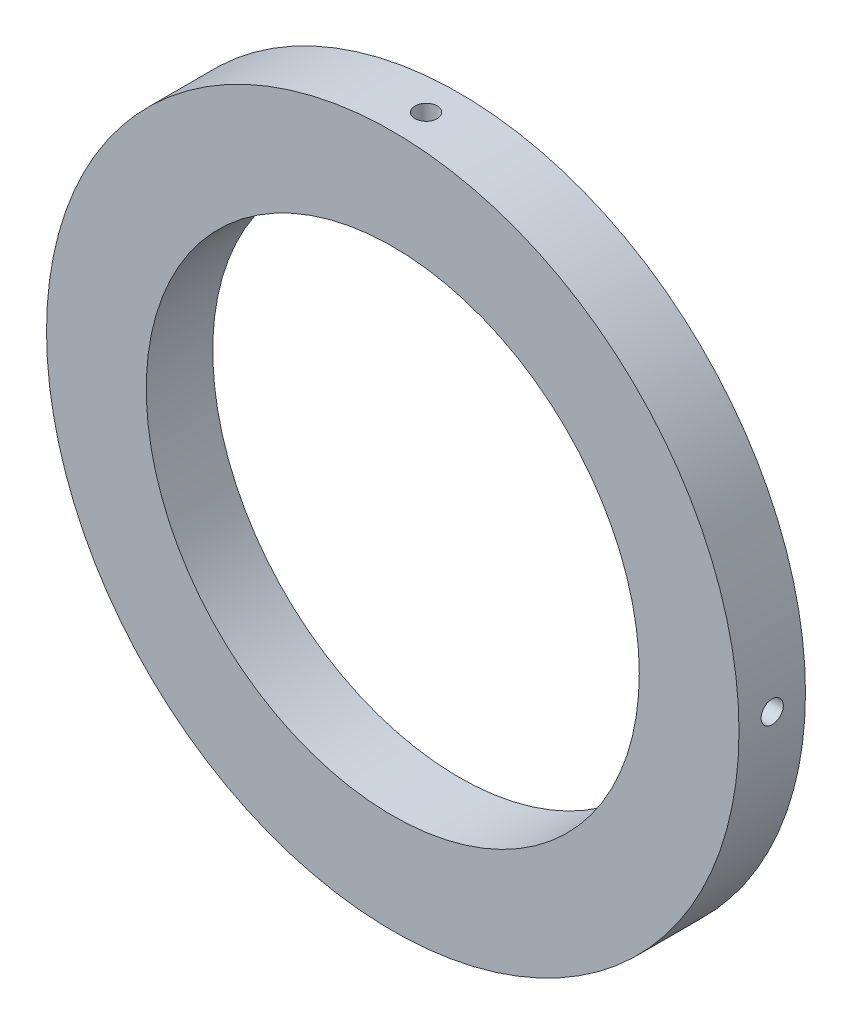
SolidWorks part; units mm, degrees
material "6063-T6"
ref_plane "Ön Düzlem" through (0, 0, 0) normal (0, 0, 1) x (1, 0, 0)
ref_plane "Üst Düzlem" through (0, 0, 0) normal (0, 1, 0) x (1, 0, 0)
ref_plane "Sağ Düzlem" through (0, 0, 0) normal (1, 0, 0) x (0, 0, -1)
sketch "Sketch1" plane through (0, 0, 0) normal (0, 0, 1) x (1, 0, 0)
  circle A0 centre (0, 0) radius 62.5
  circle A1 centre (0, 0) radius 44.5
  dimension "D1" = 125
  dimension "D2" = 89
extrude "Boss-Extrude1" add sketch "Sketch1" along normal mid plane 12
sketch "Sketch2" plane through (0, 0, 0) normal (0, 1, 0) x (1, 0, 0)
  circle A0 centre (0, 0) radius 2
  dimension "D1" = 4
extrude "Cut-Extrude1" cut sketch "Sketch2" along normal blind 10 from offset 55
extrude "Cut-Extrude2" cut sketch "Sketch2<2>" against normal blind 10 from offset 55 offset against normal yes
sketch "Sketch2<2>" plane through (0, 0, 0) normal (0, 1, 0) x (1, 0, 0) same geometry as "Sketch2"
sketch "Sketch3" plane through (0, 0, 0) normal (1, 0, 0) x (0, 0, -1)
  circle A0 centre (0, 0) radius 2
  dimension "D1" = 4
extrude "Cut-Extrude3" cut sketch "Sketch3" along normal blind 10 from offset 55
extrude "Cut-Extrude4" cut sketch "Sketch3<2>" against normal blind 10 from offset 55 offset against normal yes
sketch "Sketch3<2>" plane through (0, 0, 0) normal (1, 0, 0) x (0, 0, -1) same geometry as "Sketch3"
